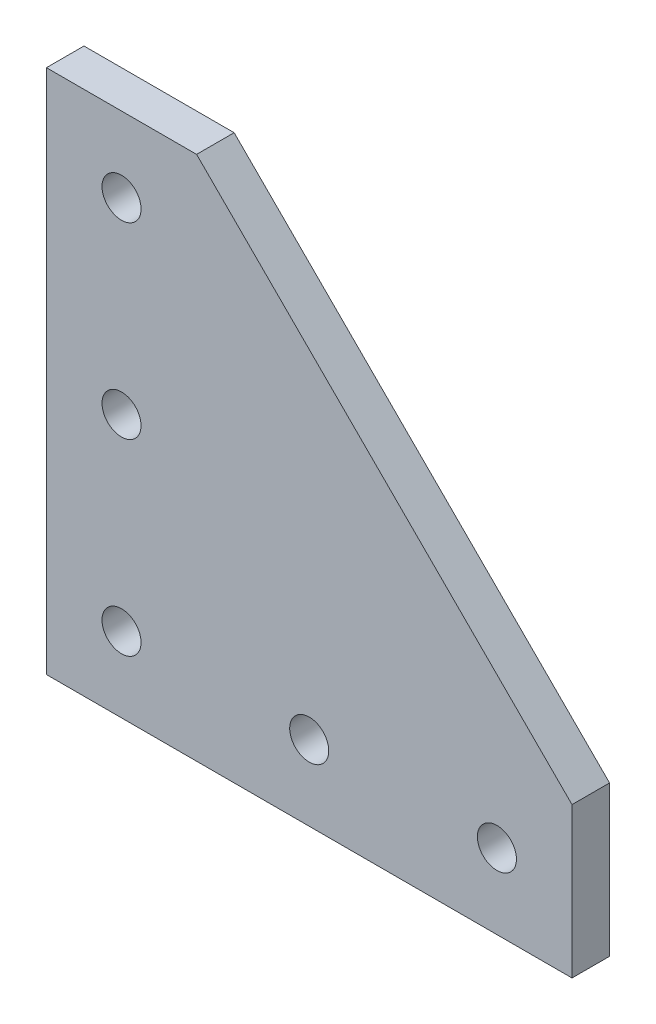
SolidWorks part; units mm, degrees
ref_plane "Front Plane" through (0, 0, 0) normal (0, 0, 1) x (1, 0, 0)
ref_plane "Top Plane" through (0, 0, 0) normal (0, 1, 0) x (1, 0, 0)
ref_plane "Right Plane" through (0, 0, 0) normal (1, 0, 0) x (0, 0, -1)
sketch "Sketch1" plane through (0, 0, 0) normal (0, 0, 1) x (1, 0, 0)
  line L0 (0, 0) -> (0, 88.9)
  line L1 (0, 88.9) -> (25.4, 88.9)
  line L2 (25.4, 88.9) -> (88.9, 25.4)
  line L3 (88.9, 25.4) -> (88.9, 0)
  line L4 (88.9, 0) -> (0, 0)
  line L5 (0, 0) -> (-0.266, -0.133)
  line L6 (12.7, 12.7) -> (12.7, 76.2) construction
  line L7 (12.7, 12.7) -> (76.2, 12.7) construction
  circle A0 centre (12.7, 12.7) radius 3.302
  circle A1 centre (12.7, 44.45) radius 3.302
  circle A2 centre (12.7, 76.2) radius 3.302
  circle A3 centre (44.45, 12.7) radius 3.302
  circle A4 centre (76.2, 12.7) radius 3.302
  dimension "D5" = 6.604
  dimension "D1" = 25.4
  dimension "D2" = 25.4
  dimension "D3" = 88.9
  dimension "D4" = 88.9
  dimension "D6" = 12.7
  dimension "D7" = 12.7
  dimension "D8" = 63.5
  dimension "D9" = 63.5
extrude "Boss-Extrude1" add sketch "Sketch1" along normal blind 6.35 contours L4 L3 L2 L1 L0 A4 A3 A2 A1 A0 region at (36.6179, 36.6179, 0)
